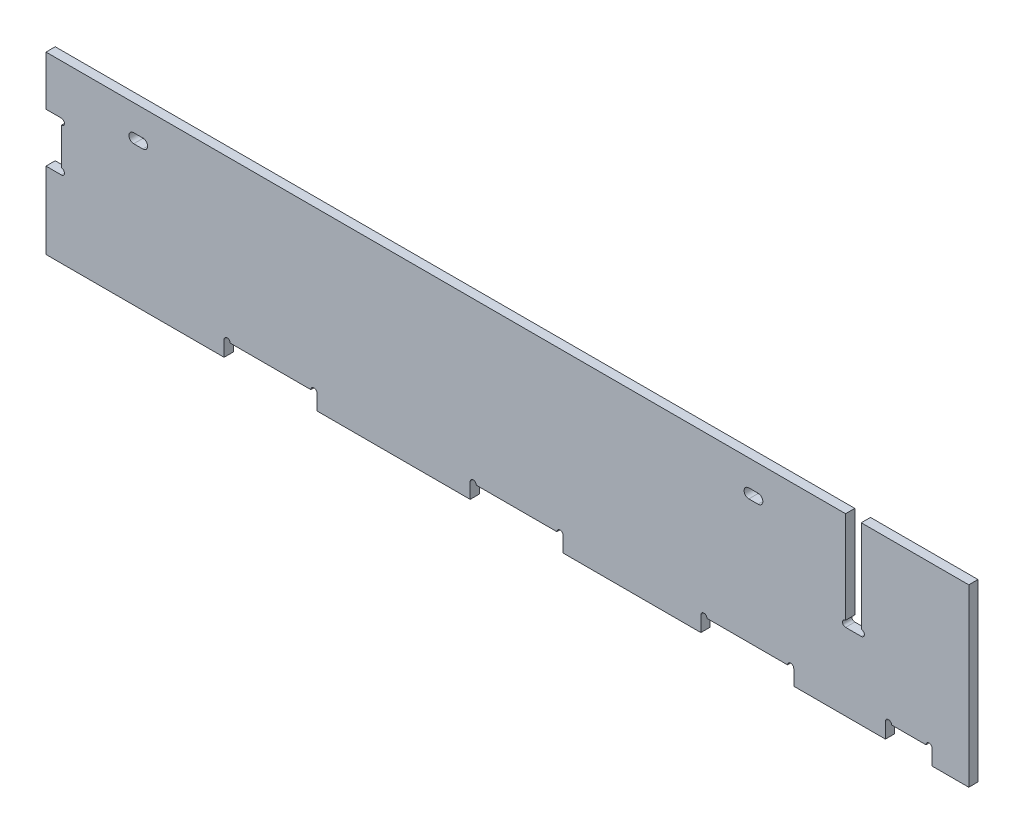
SolidWorks part; units mm, degrees
material "사용자정의 플라스틱"
ref_plane "정면" through (0, 0, 0) normal (0, 0, 1) x (1, 0, 0)
ref_plane "윗면" through (0, 0, 0) normal (0, 1, 0) x (1, 0, 0)
ref_plane "우측면" through (0, 0, 0) normal (1, 0, 0) x (0, 0, -1)
sketch "스케치1" plane through (0, 0, 0) normal (0, 0, 1) x (1, 0, 0)
  line L1 (0, 0) -> (300, 0)
  line L2 (0, 0) -> (0, 57)
  line L3 (0, 57) -> (300, 57)
  line L4 (300, 0) -> (300, 57)
  dimension "D1" = 57
  dimension "D2" = 300
extrude "보스-돌출1" add sketch "스케치1" along normal blind 3
sketch "스케치2" plane through (0, 0, 3) normal (0, 0, 1) x (1, 0, 0)
  line L0 (260, 57) -> (260, 26) construction
  line L1 (5, 40.9) -> (0, 40.9)
  line L2 (5, 40.9) -> (5, 24.9)
  line L3 (5, 24.9) -> (0, 24.9)
  line L4 (0, 40.9) -> (0, 24.9)
  line L7 (57.9, 5) -> (88.1, 5)
  line L8 (57.9, 5) -> (57.9, 0)
  line L9 (57.9, 0) -> (88.1, 0)
  line L10 (88.1, 5) -> (88.1, 0)
  line L13 (168.1, 0) -> (137.9, 0)
  line L14 (168.1, 0) -> (168.1, 5)
  line L15 (168.1, 5) -> (137.9, 5)
  line L16 (137.9, 0) -> (137.9, 5)
  line L18 (243.1, 0) -> (212.9, 0)
  line L19 (243.1, 0) -> (243.1, 5)
  line L20 (243.1, 5) -> (212.9, 5)
  line L21 (212.9, 0) -> (212.9, 5)
  line L23 (288.1, 0) -> (272.9, 0)
  line L24 (288.1, 0) -> (288.1, 5)
  line L25 (288.1, 5) -> (272.9, 5)
  line L26 (272.9, 0) -> (272.9, 5)
  line L27 (300, 57) -> (0, 57) construction
  line L28 (259.95, 57) -> (265.05, 57)
  line L29 (259.95, 57) -> (259.95, 25)
  line L30 (259.95, 25) -> (265.05, 25)
  line L31 (265.05, 57) -> (265.05, 25)
  line L33 (5, 25) -> (0, 25) construction
  line L35 (5, 40.8) -> (0, 40.8) construction
  line L36 (288, 5) -> (288, 0) construction
  line L37 (273, 5) -> (273, 0) construction
  line L38 (243, 5) -> (243, 0) construction
  line L39 (213, 5) -> (213, 0) construction
  line L40 (168, 5) -> (168, 0) construction
  line L41 (138, 5) -> (138, 0) construction
  line L42 (88, 5) -> (88, 0) construction
  line L43 (58, 5) -> (58, 0) construction
  line L44 (265, 46.85) -> (265, 15.15) construction
  dimension "D1" = 0.1
  dimension "D2" = 0.1
  dimension "D3" = 0.1
  dimension "D4" = 0.1
  dimension "D5" = 0.1
  dimension "D6" = 0.1
  dimension "D7" = 0.1
  dimension "D8" = 0.1
  dimension "D9" = 0.1
  dimension "D10" = 0.1
  dimension "D11" = 0.05
  dimension "D12" = 0.05
extrude "컷-돌출1" cut sketch "스케치2" against normal blind 5
sketch "스케치3" plane through (0, 0, 3) normal (0, 0, 1) x (1, 0, 0)
  line L1 (259.95, 25) -> (265.05, 25) construction
  line L2 (265.05, 25) -> (265.05, 57) construction
  line L3 (259.95, 57) -> (259.95, 25) construction
  line L4 (243.1, 5) -> (212.9, 5) construction
  line L5 (88.1, 5) -> (57.9, 5) construction
  line L6 (168.1, 5) -> (137.9, 5) construction
  line L7 (5, 24.9) -> (5, 40.9) construction
  line L8 (288.1, 5) -> (272.9, 5) construction
  line L9 (272.9, 5) -> (272.9, 0) construction
  line L10 (288.1, 0) -> (288.1, 5) construction
  circle A0 centre (273.9, 5) radius 1
  circle A1 centre (287.1, 5) radius 1
  circle A2 centre (259.95, 26) radius 1
  circle A3 centre (265.05, 26) radius 1
  circle A6 centre (213.9, 5) radius 1
  circle A7 centre (242.1, 5) radius 1
  circle A8 centre (87.1, 5) radius 1
  circle A9 centre (138.9, 5) radius 1
  circle A10 centre (167.1, 5) radius 1
  circle A11 centre (5, 25.9) radius 1
  circle A12 centre (5, 39.9) radius 1
  circle A13 centre (58.9, 5) radius 1
  dimension "D1" = 2
  dimension "D2" = 2
extrude "컷-돌출2" cut sketch "스케치3" against normal blind 5
sketch "스케치5" plane through (0, 0, 3) normal (0, 0, 1) x (1, 0, 0)
  line L0 (43.45, 57) -> (43.45, 49)
  line L1 (46.55, 45) -> (43.45, 45) construction
  line L2 (47.75, 49) -> (47.75, 46.2) construction
  line L3 (43.45, 49) -> (43.45, 46.2) construction
  line L4 (46.55, 57) -> (43.45, 57)
  line L5 (47.75, 46.2) -> (46.55, 46.2)
  line L6 (46.55, 57) -> (46.55, 49)
  line L7 (42.25, 46.2) -> (42.25, 49) construction
  line L8 (46.55, 49) -> (47.75, 49)
  line L9 (46.55, 46.2) -> (46.55, 49) construction
  line L10 (43.45, 46.2) -> (43.45, 45)
  line L11 (46.55, 49) -> (43.45, 49) construction
  line L12 (46.55, 46.2) -> (43.45, 46.2) construction
  line L13 (43.45, 46.2) -> (42.25, 46.2)
  line L14 (46.55, 46.2) -> (46.55, 45)
  line L15 (45, 45) -> (45, 43.45) construction
  line L16 (42.25, 49) -> (43.45, 49)
  line L17 (47.75, 47.6) -> (46.55, 47.6) construction
  line L18 (42.25, 47.6) -> (43.45, 47.6) construction
  line L19 (45, 46.2) -> (45, 45) construction
  line L20 (42.25, 47.6) -> (40.85, 47.6) construction
  line L21 (47.75, 47.6) -> (49.15, 47.6) construction
  line L22 (0, 57) -> (45, 57) construction
  line L23 (300, 57) -> (265.05, 57) construction
  line L24 (45, 57) -> (150, 57) construction
  line L25 (150, 57) -> (255, 57) construction
  line L26 (255, 57) -> (300, 57) construction
  line L49 (151.55, 49) -> (152.75, 49)
  line L50 (151.55, 49) -> (148.45, 49) construction
  line L51 (148.45, 46.2) -> (148.45, 45)
  line L52 (147.25, 46.2) -> (147.25, 49) construction
  line L53 (148.45, 57) -> (148.45, 49)
  line L54 (151.55, 57) -> (151.55, 49)
  line L55 (151.55, 46.2) -> (151.55, 45)
  line L56 (150, 46.2) -> (150, 45) construction
  line L57 (151.55, 46.2) -> (151.55, 49) construction
  line L58 (152.75, 47.6) -> (154.15, 47.6) construction
  line L59 (152.75, 46.2) -> (151.55, 46.2)
  line L60 (148.45, 49) -> (148.45, 46.2) construction
  line L61 (147.25, 47.6) -> (145.85, 47.6) construction
  line L62 (151.55, 57) -> (148.45, 57)
  line L63 (148.45, 46.2) -> (147.25, 46.2)
  line L64 (151.55, 46.2) -> (148.45, 46.2) construction
  line L65 (151.55, 45) -> (148.45, 45) construction
  line L66 (147.25, 47.6) -> (148.45, 47.6) construction
  line L67 (147.25, 49) -> (148.45, 49)
  line L68 (152.75, 49) -> (152.75, 46.2) construction
  line L69 (150, 45) -> (150, 43.45) construction
  line L70 (152.75, 47.6) -> (151.55, 47.6) construction
  line L71 (256.55, 49) -> (257.75, 49)
  line L72 (256.55, 49) -> (253.45, 49) construction
  line L73 (253.45, 46.2) -> (253.45, 45)
  line L74 (252.25, 46.2) -> (252.25, 49) construction
  line L75 (253.45, 57) -> (253.45, 49)
  line L76 (256.55, 57) -> (256.55, 49)
  line L77 (256.55, 46.2) -> (256.55, 45)
  line L78 (255, 46.2) -> (255, 45) construction
  line L79 (256.55, 46.2) -> (256.55, 49) construction
  line L80 (257.75, 47.6) -> (259.15, 47.6) construction
  line L81 (257.75, 46.2) -> (256.55, 46.2)
  line L82 (253.45, 49) -> (253.45, 46.2) construction
  line L83 (252.25, 47.6) -> (250.85, 47.6) construction
  line L84 (256.55, 57) -> (253.45, 57)
  line L85 (253.45, 46.2) -> (252.25, 46.2)
  line L86 (256.55, 46.2) -> (253.45, 46.2) construction
  line L87 (256.55, 45) -> (253.45, 45) construction
  line L88 (252.25, 47.6) -> (253.45, 47.6) construction
  line L89 (252.25, 49) -> (253.45, 49)
  line L90 (257.75, 49) -> (257.75, 46.2) construction
  line L91 (255, 45) -> (255, 43.45) construction
  line L92 (257.75, 47.6) -> (256.55, 47.6) construction
  arc A0 (43.45, 45) -> (46.55, 45) centre (45, 45) ccw
  arc A1 (47.75, 46.2) -> (47.75, 49) centre (47.75, 47.6) ccw
  arc A2 (42.25, 49) -> (42.25, 46.2) centre (42.25, 47.6) ccw
  arc A6 (152.75, 46.2) -> (152.75, 49) centre (152.75, 47.6) ccw
  arc A7 (147.25, 49) -> (147.25, 46.2) centre (147.25, 47.6) ccw
  arc A8 (148.45, 45) -> (151.55, 45) centre (150, 45) ccw
  arc A9 (257.75, 46.2) -> (257.75, 49) centre (257.75, 47.6) ccw
  arc A10 (252.25, 49) -> (252.25, 46.2) centre (252.25, 47.6) ccw
  arc A11 (253.45, 45) -> (256.55, 45) centre (255, 45) ccw
  dimension "D1" = 3.1
  dimension "D2" = 5.5
  dimension "D3" = 2.8
  dimension "D4" = 1.2
  dimension "D5" = 8
  dimension "D6" = 3.1
  dimension "D7" = 45
  dimension "D14" = 3.1
  dimension "D15" = 5.5
  dimension "D16" = 2.8
  dimension "D17" = 1.2
  dimension "D18" = 8
  dimension "D19" = 3.1
  dimension "D20" = 3.1
  dimension "D21" = 5.5
  dimension "D22" = 2.8
  dimension "D23" = 1.2
  dimension "D24" = 8
  dimension "D25" = 3.1
extrude "컷-돌출4" [suppressed] cut sketch "스케치5" against normal blind 10
sketch "스케치7" plane through (0, 0, 3) normal (0, 0, 1) x (1, 0, 0)
  line L0 (259.95, 57) -> (259.95, 27) construction
  line L1 (259.85, 33.9113) -> (265.15, 33.9113)
  line L2 (259.85, 33.9113) -> (259.85, 16.1106)
  line L3 (259.85, 16.1106) -> (265.15, 16.1106)
  line L4 (265.15, 33.9113) -> (265.15, 16.1106)
  line L5 (265.05, 27) -> (265.05, 57) construction
  dimension "D1" = 0.1
  dimension "D2" = 0.1
extrude "컷-돌출5" [suppressed] cut sketch "스케치7" against normal blind 10
sketch "스케치8" plane through (0, 0, 3) normal (0, 0, 1) x (1, 0, 0)
  line L0 (28.5, 47) -> (31.5, 47) construction
  line L1 (28.5, 48.55) -> (31.5, 48.55)
  line L2 (28.5, 45.45) -> (31.5, 45.45)
  line L3 (228.5, 47) -> (231.5, 47) construction
  line L4 (228.5, 48.55) -> (231.5, 48.55)
  line L5 (228.5, 45.45) -> (231.5, 45.45)
  line L6 (230, 47) -> (30, 47) construction
  line L7 (30, 47) -> (0, 47) construction
  line L8 (0, 57) -> (0, 40.9) construction
  line L9 (300, 57) -> (265.05, 57) construction
  arc A0 (28.5, 48.55) -> (28.5, 45.45) centre (28.5, 47) ccw
  arc A1 (31.5, 45.45) -> (31.5, 48.55) centre (31.5, 47) ccw
  arc A2 (228.5, 48.55) -> (228.5, 45.45) centre (228.5, 47) ccw
  arc A3 (231.5, 45.45) -> (231.5, 48.55) centre (231.5, 47) ccw
  point P2 (30, 47)
  point P7 (230, 47)
  dimension "D2" = 1.55
  dimension "D1" = 10
  dimension "D3" = 3
  dimension "D4" = 200
  dimension "D5" = 30
extrude "컷-돌출6" cut sketch "스케치8" against normal blind 10
